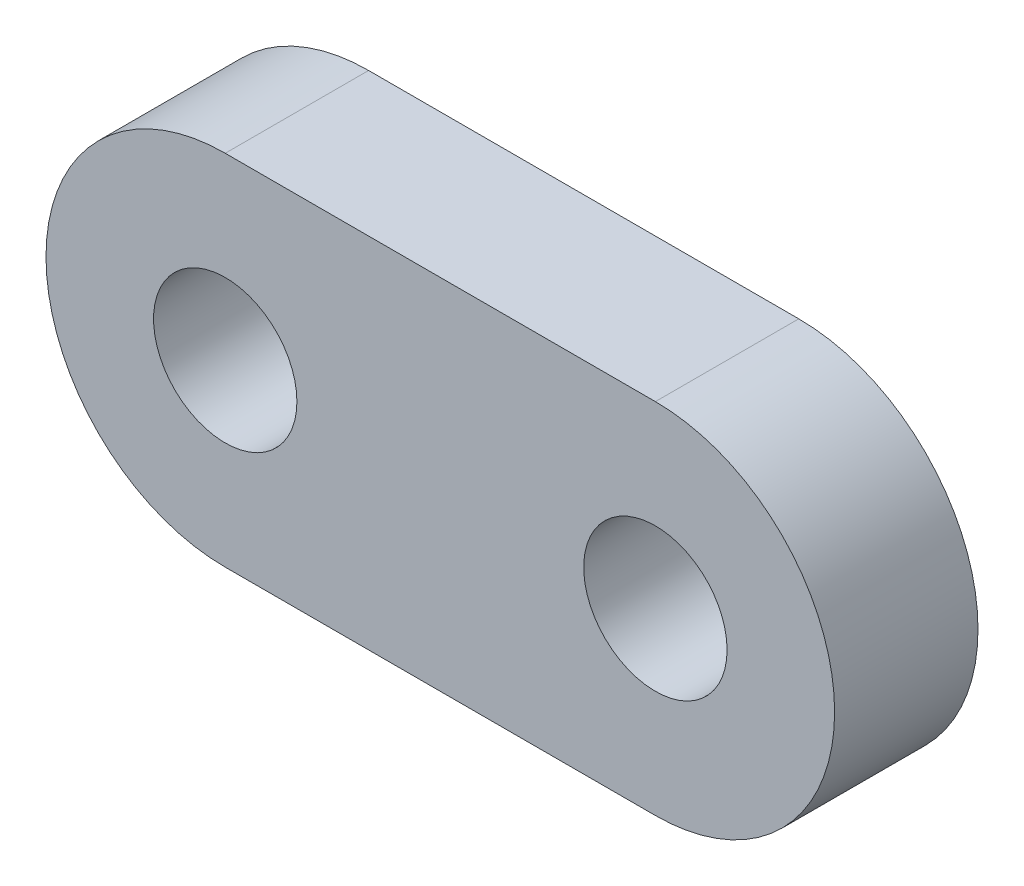
SolidWorks part; units mm, degrees
material "ABS"
ref_plane "Front Plane" through (0, 0, 0) normal (0, 0, 1) x (1, 0, 0)
ref_plane "Top Plane" through (0, 0, 0) normal (0, 1, 0) x (1, 0, 0)
ref_plane "Right Plane" through (0, 0, 0) normal (1, 0, 0) x (0, 0, -1)
sketch "Sketch1" plane through (0, 0, 0) normal (0, 0, 1) x (1, 0, 0)
  line L0 (0, 3.175) -> (7.62, 3.175)
  line L1 (0, -3.175) -> (7.62, -3.175)
  circle A0 centre (0, 0) radius 1.27
  circle A1 centre (0, 0) radius 3.175
  circle A2 centre (7.62, 0) radius 1.27
  circle A3 centre (7.62, 0) radius 3.175
  dimension "D1" = 2.54
  dimension "D2" = 6.35
  dimension "D3" = 7.62
extrude "Boss-Extrude1" add sketch "Sketch1" along normal blind 2.54 contours A3 L0 A1 L1 | A1 A0 | A3 A2 region at (3.81, 0, 0) region at (2.1816, 2.1816, 0) region at (9.8016, 2.1816, 0)
